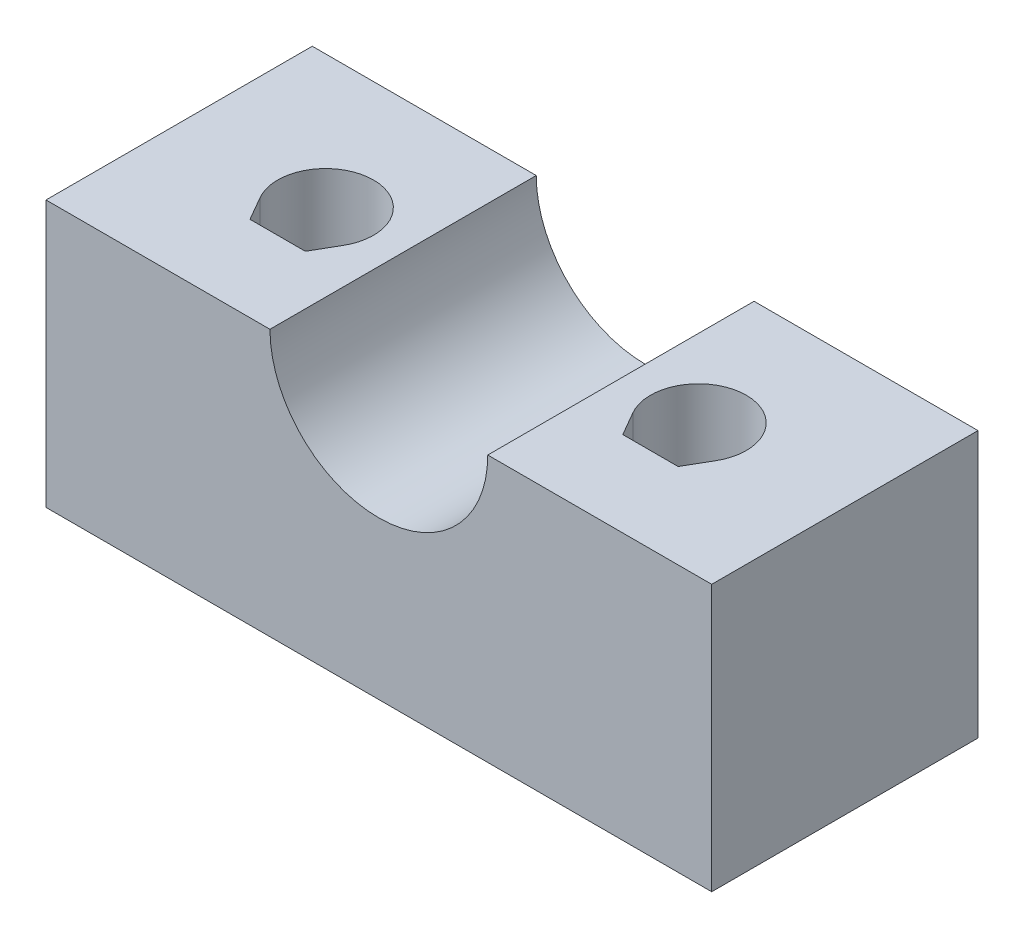
SolidWorks part; units mm, degrees
ref_plane "Piano frontale" through (0, 0, 0) normal (0, 0, 1) x (1, 0, 0)
ref_plane "Piano superiore" through (0, 0, 0) normal (0, 1, 0) x (1, 0, 0)
ref_plane "Piano destro" through (0, 0, 0) normal (1, 0, 0) x (0, 0, -1)
sketch "Schizzo1" plane through (0, 0, 0) normal (0, 0, 1) x (1, 0, 0)
  line L0 (0, 5) -> (0, -5) construction
  line L1 (-12.5, -5) -> (12.5, -5)
  line L2 (-12.5, -5) -> (-12.5, 5)
  line L3 (-12.5, 5) -> (-4.09, 5)
  line L4 (12.5, -5) -> (12.5, 5)
  line L5 (-12.5, -5) -> (12.5, 5) construction
  line L6 (-12.5, 5) -> (12.5, -5) construction
  line L7 (4.09, 5) -> (12.5, 5)
  line L8 (-4.09, 5) -> (4.09, 5) construction
  arc A0 (-4.09, 5) -> (4.09, 5) centre (0, 5) ccw
  point P0 (0, 0)
  dimension "D3" = 4.09
  dimension "D1" = 10
  dimension "D2" = 25
extrude "Main body" add sketch "Schizzo1" along normal mid plane 10 contours L7 L4 L1 L2 L3 A0
sketch "Schizzo2" plane through (0, -5, 0) normal (0, -1, 0) x (1, 0, 0)
  line L0 (0, 5) -> (0, -5) construction
  line L1 (-12.5, 5) -> (12.5, 5) construction
  line L2 (-12.5, -5) -> (12.5, -5) construction
  line L3 (-12.5, 0) -> (12.5, 0) construction
  line L4 (-12.5, 5) -> (-12.5, -5) construction
  line L5 (12.5, 5) -> (12.5, -5) construction
  line L6 (-7, -1.8) -> (-7, 1.8) construction
  line L7 (-5.9608, 1.8) -> (-5.4412, 0.9)
  line L8 (-8.0392, 1.8) -> (-8.5588, 0.9)
  line L9 (-5.9608, 1.8) -> (-8.0392, 1.8)
  line L10 (5.9608, 1.8) -> (8.0392, 1.8)
  line L11 (8.0392, 1.8) -> (8.5588, 0.9)
  line L12 (5.9608, 1.8) -> (5.4412, 0.9)
  arc A0 (-8.5588, 0.9) -> (-5.4412, 0.9) centre (-7, 0) ccw
  arc A1 (8.5588, 0.9) -> (5.4412, 0.9) centre (7, 0) cw
  point P22 (7, 1.8)
  point P24 (-7, 1.8)
  dimension "D2" = 3.6
  dimension "D1" = 7
  dimension "D3" = 120
extrude "screw holes" cut sketch "Schizzo2" against normal up to next contours A0 L7 L9 L8 | A1 L12 L10 L11
ref_axis "y rod axis" through (0, 5, 5) along (0, 0, -1)
ref_axis "Screw1 hole" through (7, 5, 0) along (0, -1, 0)
ref_axis "Screw 2 hole" through (-7, 5, 0) along (0, -1, 0)
